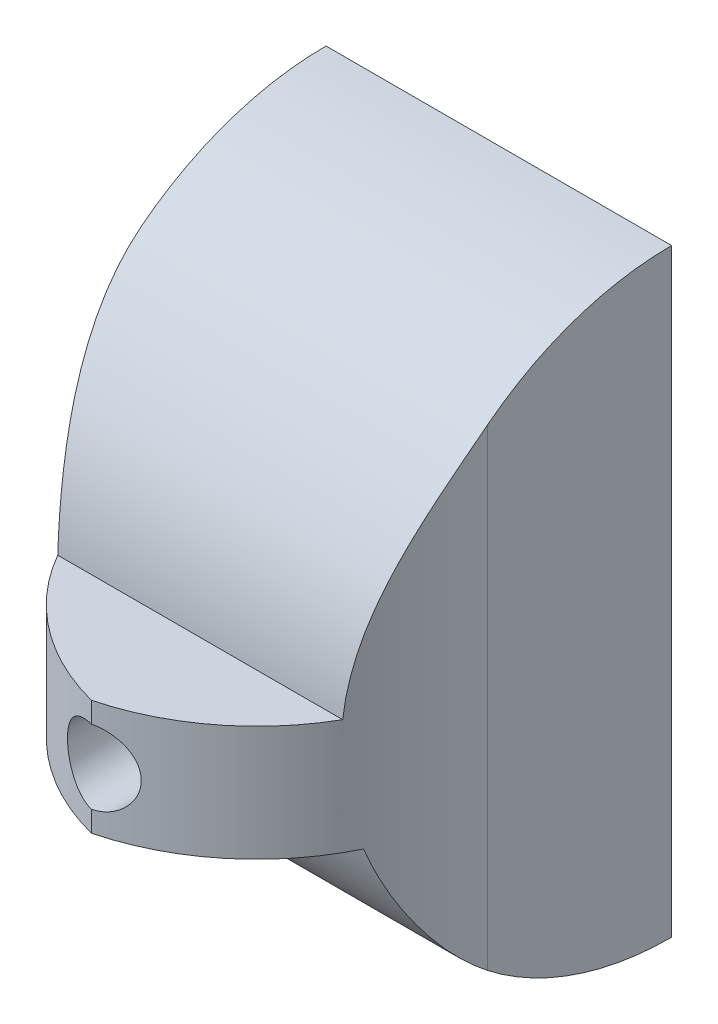
SolidWorks part; units mm, degrees
ref_plane "Front Plane" through (0, 0, 0) normal (0, 0, 1) x (1, 0, 0)
ref_plane "Top Plane" through (0, 0, 0) normal (0, 1, 0) x (1, 0, 0)
ref_plane "Right Plane" through (0, 0, 0) normal (1, 0, 0) x (0, 0, -1)
sketch "Sketch1" plane through (0, 0, 0) normal (0, 0, 1) x (1, 0, 0)
  line L1 (0, 0) -> (15, 0)
  line L2 (0, 0) -> (0, 26)
  line L3 (0, 26) -> (15, 26)
  line L4 (15, 0) -> (15, 26)
  dimension "D1" = 15
  dimension "D2" = 26
extrude "Boss-Extrude1" add sketch "Sketch1" along normal blind 18
ref_plane "Plane1" through (13, 0, 0) normal (1, 0, 0) x (0, 0, -1)
sketch "Sketch2" plane through (13, 0, 0) normal (1, 0, 0) x (0, 0, -1)
  line L0 (0, 26) -> (0, 0) construction
  circle A0 centre (0, 13) radius 4
  dimension "D1" = 8
ref_plane "Plane3" through (12, 0, 0) normal (1, 0, 0) x (0, 0, -1)
extrude "Cut-Extrude1" cut sketch "Sketch2" against normal blind 11
sketch "Sketch3" plane through (12, 0, 0) normal (1, 0, 0) x (0, 0, -1)
  line L0 (0, 0) -> (0, 26) construction
  circle A0 centre (0, 13) radius 12
  dimension "D1" = 24
extrude "Cut-Extrude2" cut sketch "Sketch3" against normal blind 9
sketch "Sketch4" plane through (15, 0, 0) normal (1, 0, 0) x (0, 0, -1)
  line L0 (0, 0) -> (0, 26) construction
  line L1 (0, 13) -> (-18, 13) construction
  line L2 (-18, 0) -> (-18, 26) construction
  line L3 (-20.4238, 14) -> (-12.9615, 14)
  line L4 (-20.4238, 14) -> (-20.4238, 9)
  line L5 (-20.4238, 9) -> (-12.3693, 9)
  line L7 (-30.3733, 32.1118) -> (15.3918, 32.1118)
  line L8 (-30.3733, 32.1118) -> (-30.3733, -3.5348)
  line L9 (-30.3733, -3.5348) -> (15.3918, -3.5348)
  line L10 (15.3918, 32.1118) -> (15.3918, -3.5348)
  arc A0 (-12.3693, 9) -> (-12.9615, 14) centre (0, 13) ccw
  dimension "D1" = 1
  dimension "D2" = 5
extrude "Cut-Extrude3" cut sketch "Sketch4" against normal up to next
sketch "Sketch5" plane through (0, 0, 18) normal (0, 0, 1) x (1, 0, 0)
  line L0 (0, 14) -> (0, 9) construction
  circle A0 centre (7.5, 11.5) radius 1.6
  point P4 (0, 11.5)
  dimension "D1" = 3.2
fillet "Fillet1" radius 10 2 edges at (15, 11.5, 18) (0, 11.5, 18)
extrude "Cut-Extrude4" cut sketch "Sketch5" against normal blind 5
